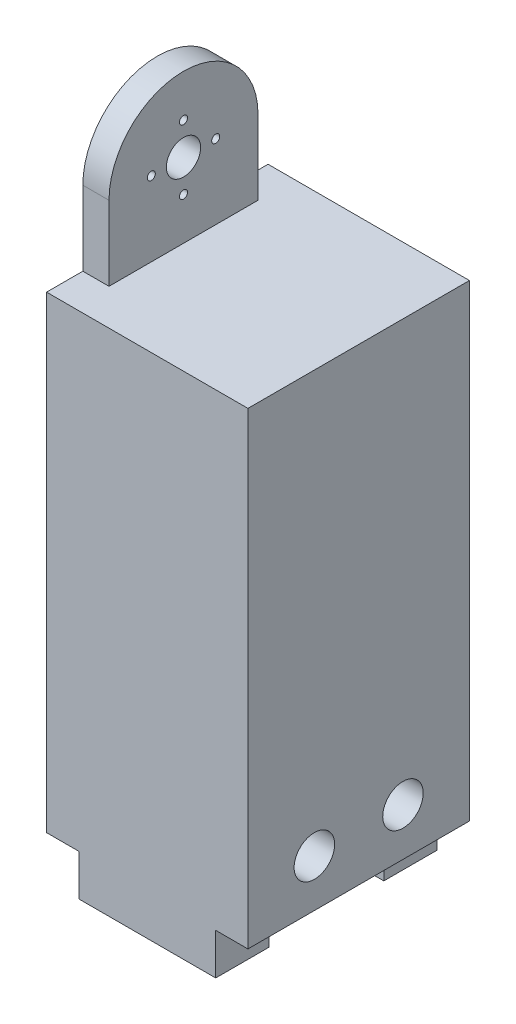
SolidWorks part; units mm, degrees
ref_plane "Front Plane" through (0, 0, 0) normal (0, 0, 1) x (1, 0, 0)
ref_plane "Top Plane" through (0, 0, 0) normal (0, 1, 0) x (1, 0, 0)
ref_plane "Right Plane" through (0, 0, 0) normal (1, 0, 0) x (0, 0, -1)
sketch "Sketch1" plane through (0, 0, 0) normal (0, 0, 1) x (1, 0, 0)
  line L1 (-25, 0) -> (25, 0)
  line L2 (-25, 0) -> (-25, -150)
  line L3 (-25, -150) -> (25, -150)
  line L4 (25, 0) -> (25, -150)
  dimension "D1" = 50
  dimension "D2" = 150
extrude "Boss-Extrude1" add sketch "Sketch1" against normal blind 55
sketch "Sketch2" plane through (25, 0, 0) normal (1, 0, 0) x (0, 0, -1)
  line L0 (55, 0) -> (0, 0) construction
  line L1 (0, -150) -> (0, 0) construction
  circle A0 centre (27.5, -25) radius 10.25
  dimension "D1" = 25
  dimension "D2" = 27.5
extrude "Cut-Extrude1" cut sketch "Sketch2" against normal blind 45 and the other way through all
sketch "Sketch7" plane through (-20, 0, 0) normal (1, 0, 0) x (0, 0, -1)
  line L0 (27.5, -17) -> (27.5, -33) construction
  circle A0 centre (27.5, -25) radius 8
  circle A1 centre (27.5, -17) radius 1
  circle A2 centre (35.5, -25) radius 1
  circle A3 centre (27.5, -33) radius 1
  circle A4 centre (19.5, -25) radius 1
  circle A5 centre (27.5, -25) radius 4.25
  point P14 (27.5, -25)
  dimension "D1" = 16
  dimension "D2" = 2
  dimension "D4" = 8.5
  dimension "D3" = 4
extrude "Cut-Extrude3" cut sketch "Sketch7" against normal blind 10 contours L0 A0 A1 | A0 A1 | A0 L0 A1 | A0 A4 | A0 A4 | L0 A3 A0 | A3 L0 A0 | A0 A3 | A0 A2 | A0 A2 | A5 L0 | L0 A5 region at (-20, -17.4355, -27.9155) region at (-20, -16.587, -27.5) region at (-20, -17.4355, -27.0845) region at (-20, -25, -29.3038) region at (-20, -25, -25.6962) region at (-20, -25, -35.913) region at (-20, -25, -35.0645) region at (-20, -25, -19.9355) region at (-20, -25, -19.087) region at (-20, -32.5645, -27.9155) region at (-20, -32.5645, -27.0845) region at (-20, -33.413, -27.5)
sketch "Sketch8" plane through (25, 0, 0) normal (1, 0, 0) x (0, 0, -1)
  line L1 (55, -150) -> (55, 0) construction
  line L3 (0, -150) -> (55, -150)
  line L4 (0, -150) -> (0, -205)
  line L5 (0, -205) -> (55, -205)
  line L6 (55, -150) -> (55, -205)
  circle A1 centre (27.5, -180) radius 10.25
  circle A3 centre (27.5, -25) radius 10.25 construction
  dimension "D1" = 27.5
  dimension "D2" = 155
  dimension "D3" = 25
extrude "Boss-Extrude2" add sketch "Sketch8" against normal blind 50
sketch "Sketch10" plane through (0, 0, 0) normal (0, 0, 1) x (1, 0, 0)
  line L0 (-25, -205) -> (25, -205) construction
  line L5 (17, -205) -> (-17, -205)
  line L6 (17, -205) -> (17, -144.75)
  line L8 (-17, -205) -> (-17, -144.75)
  line L9 (-25, 0) -> (-25, -205) construction
  line L10 (-25, -180) -> (25, -180)
  line L13 (25, -169.75) -> (-25, -169.75)
  line L14 (25, -169.75) -> (25, -190.25)
  line L15 (25, -190.25) -> (-25, -190.25)
  line L16 (-25, -169.75) -> (-25, -190.25)
  line L17 (25, -205) -> (25, 0) construction
  line L18 (0, -180) -> (17, -180)
  line L19 (0, -180) -> (0, -191.25)
  line L20 (0, -191.25) -> (17, -191.25)
  line L21 (17, -180) -> (17, -191.25)
  line L22 (17, -191.25) -> (-17, -191.25)
  line L23 (17, -191.25) -> (17, -169.75)
  line L24 (17, -169.75) -> (-17, -169.75)
  line L25 (-17, -191.25) -> (-17, -169.75)
  line L26 (17, -191.25) -> (-17, -191.25)
  line L27 (17, -191.25) -> (17, -144.75)
  line L28 (17, -144.75) -> (-17, -144.75)
  line L29 (-17, -191.25) -> (-17, -144.75)
  line L30 (-25, -169.75) -> (-17, -169.75)
  line L31 (-25, -169.75) -> (-25, -205)
  line L32 (-25, -205) -> (-17, -205)
  line L33 (-17, -169.75) -> (-17, -205)
  line L34 (25, -169.75) -> (17, -169.75)
  line L35 (25, -169.75) -> (25, -205)
  line L36 (25, -205) -> (17, -205)
  line L37 (17, -169.75) -> (17, -205)
  line L38 (-25, -169.75) -> (25, -169.75)
  line L39 (-25, -169.75) -> (-25, -164.75)
  line L40 (-25, -164.75) -> (25, -164.75)
  line L41 (25, -169.75) -> (25, -164.75)
  line M7 (-25, 0) -> (-25, -205)
  line M8 (-25, -205) -> (25, -205)
  line M9 (25, -205) -> (25, 0)
  dimension "D1" = 8
  dimension "D2" = 8
  dimension "D3" = 11.25
  dimension "D4" = 46.5
  dimension "D5" = 60.25
  dimension "D6" = 5
extrude "Cut-Extrude4" cut sketch "Sketch10" against normal through all contours L20 L22 L8 L6 M8 | L8 L15 M7 M8 | L15 L6 M9 M8 | L15 L8 L10 M7 | L8 L13 L10 M7 | L13 L6 L10 M9 | L15 L10 L6 M9 | L19 L10 L8 L15 | L10 L19 L15 L6 | L6 L13 L8 L10 | L22 L19 L15 L8 | L19 L20 L6 L15 | L29 L40 L27 L28 | L40 L8 L13 L6 region at (0, -198.125, 0) region at (21, -197.625, 0) region at (-21, -197.625, 0) region at (8.5, -190.75, 0) region at (-8.5, -190.75, 0) region at (8.5, -185.125, 0) region at (21, -185.125, 0) region at (-21, -185.125, 0) region at (-8.5, -185.125, 0) region at (0, -174.875, 0) region at (21, -174.875, 0) region at (-21, -174.875, 0) region at (0, -167.25, 0) region at (0, -154.75, 0)
sketch "Sketch11" plane through (0, -144.75, 0) normal (0, -1, 0) x (1, 0, 0)
  line L0 (17, -55) -> (17, 0) construction
  line L1 (-17, 0) -> (17, 0)
  line L2 (-17, 0) -> (-17, -13.25)
  line L3 (-17, -13.25) -> (17, -13.25)
  line L4 (17, 0) -> (17, -13.25)
  line L5 (25, -27.5) -> (-30.9131, -27.5) construction
  line L6 (25, -55) -> (25, 0) construction
  line L7 (17, -55) -> (17, -41.75)
  line L8 (-17, -41.75) -> (17, -41.75)
  line L9 (-17, -55) -> (-17, -41.75)
  line L10 (-17, -55) -> (17, -55)
  dimension "D1" = 14.25
extrude "Boss-Extrude4" add sketch "Sketch11" along normal blind 25
sketch "Sketch13" plane through (25, 0, 0) normal (1, 0, 0) x (0, 0, -1)
  line L0 (0, -169.75) -> (0, 0) construction
  line L1 (55, -169.75) -> (0, -169.75)
  line L2 (55, -169.75) -> (55, -159.75)
  line L3 (55, -159.75) -> (0, -159.75)
  line L4 (0, -169.75) -> (0, -159.75)
  dimension "D1" = 10
extrude "Cut-Extrude5" cut sketch "Sketch13" against normal blind 8
ref_plane "Plane2" through (0, 0, 0) normal (1, 0, 0) x (0, 0, -1)
mirror "Mirror2" about plane through (0, 0, 0) normal (1, 0, 0) of "Cut-Extrude5"
sketch "Sketch14" plane through (25, 0, 0) normal (1, 0, 0) x (0, 0, -1)
  line L0 (55, -159.75) -> (0, -159.75) construction
  line L1 (0, -159.75) -> (0, 0) construction
  circle A1 centre (16.5, -148) radius 5.0302
  circle A2 centre (38.5, -148) radius 5.0302
  dimension "D1" = 16.5
  dimension "D2" = 2
  dimension "D3" = 11.75
extrude "Cut-Extrude6" cut sketch "Sketch14" against normal blind 8
mirror "Mirror3" about plane through (0, 0, 0) normal (1, 0, 0) of "Cut-Extrude6"
sketch "Sketch15" plane through (0, 0, 0) normal (0, 0, 1) x (1, 0, 0)
  line L0 (-25, 0) -> (25, 0)
  line L1 (25, 0) -> (0, 0)
  line L3 (-17, -169.75) -> (17, -169.75)
  line L4 (-17, -169.75) -> (-17, -170)
  line L5 (-17, -170) -> (17, -170)
  line L6 (17, -169.75) -> (17, -170)
  line M5 (-17, -169.75) -> (17, -169.75)
  dimension "D1" = 0.25
extrude "Boss-Extrude5" add sketch "Sketch15" against normal blind 13.25 contours L6 L4 L5 M5 region at (0, -169.875, 0)
ref_plane "Plane3" through (0, 0, -27.5) normal (0, 0, 1) x (1, 0, 0)
mirror "Mirror4" about plane through (0, 0, -27.5) normal (0, 0, 1) of "Boss-Extrude5"
sketch "Sketch16" plane through (0, 0, 0) normal (0, 0, 1) x (1, 0, 0)
  line L7 (-20, -14.75) -> (-18.5, -14.75)
  line L8 (-20, -14.75) -> (-20, -35.25)
  line L9 (-20, -35.25) -> (-18.5, -35.25)
  line L10 (-18.5, -14.75) -> (-18.5, -35.25)
  line L11 (25, 0) -> (-18.5, 0)
  line L12 (25, 0) -> (25, -43.5)
  line L13 (25, -43.5) -> (-18.5, -43.5)
  line L14 (-18.5, 0) -> (-18.5, -43.5)
  line M12 (25, -159.75) -> (25, 0)
  line M13 (25, 0) -> (-25, 0)
  dimension "D1" = 1.5
  dimension "D2" = 43.5
  dimension "D3" = 43.5
extrude "Cut-Extrude7" cut sketch "Sketch16" against normal through all contours L14 L10 L13 M13 M12 region at (3.25, -21.75, 0)
sketch "Sketch19" plane through (-20, 0, 0) normal (1, 0, 0) x (0, 0, -1)
  circle A0 centre (27.5, -25) radius 4.25
  circle A1 centre (35.5, -25) radius 1
  circle A2 centre (27.5, -33) radius 1
  circle A3 centre (19.5, -25) radius 1
  circle A4 centre (27.5, -17) radius 1
  point P15 (27.5, -25)
  circle M5 centre (27.5, -25) radius 4.25
  circle M6 centre (27.5, -17) radius 1
  circle M7 centre (35.5, -25) radius 1
  circle M8 centre (27.5, -33) radius 1
  circle M9 centre (19.5, -25) radius 1
  circle M10 centre (27.5, -25) radius 10.25
  dimension "D1" = 4
extrude "Boss-Extrude6" add sketch "Sketch19" along normal blind 1.5 contours M10 M6 M8 M9 M7 M5 region at (-20, -25, -17.5399)
sketch "Sketch20" plane through (-18.5, 0, 0) normal (1, 0, 0) x (0, 0, -1)
  line L0 (9, -25) -> (9, -43.5)
  line L1 (55, -43.5) -> (0, -43.5) construction
  line L2 (9, -43.5) -> (0, -43.5)
  line L3 (46, -25) -> (46, -43.5)
  line L4 (46, -43.5) -> (55, -43.5)
  line L6 (0, 0) -> (55, 0)
  line L7 (0, 0) -> (0, -43.5)
  line L8 (0, -43.5) -> (55, -43.5)
  line L9 (55, 0) -> (55, -43.5)
  circle A0 centre (27.5, -25) radius 18.5
  line M1 (0, 0) -> (0, -43.5)
  line M2 (0, -43.5) -> (55, -43.5)
  line M3 (55, -43.5) -> (55, 0)
  line M4 (55, 0) -> (0, 0)
extrude "Cut-Extrude8" cut sketch "Sketch20" against normal through all contours A0 L3 L0 M2 M3 M4 M1 region at (-18.5, -34.25, -8.2988)
